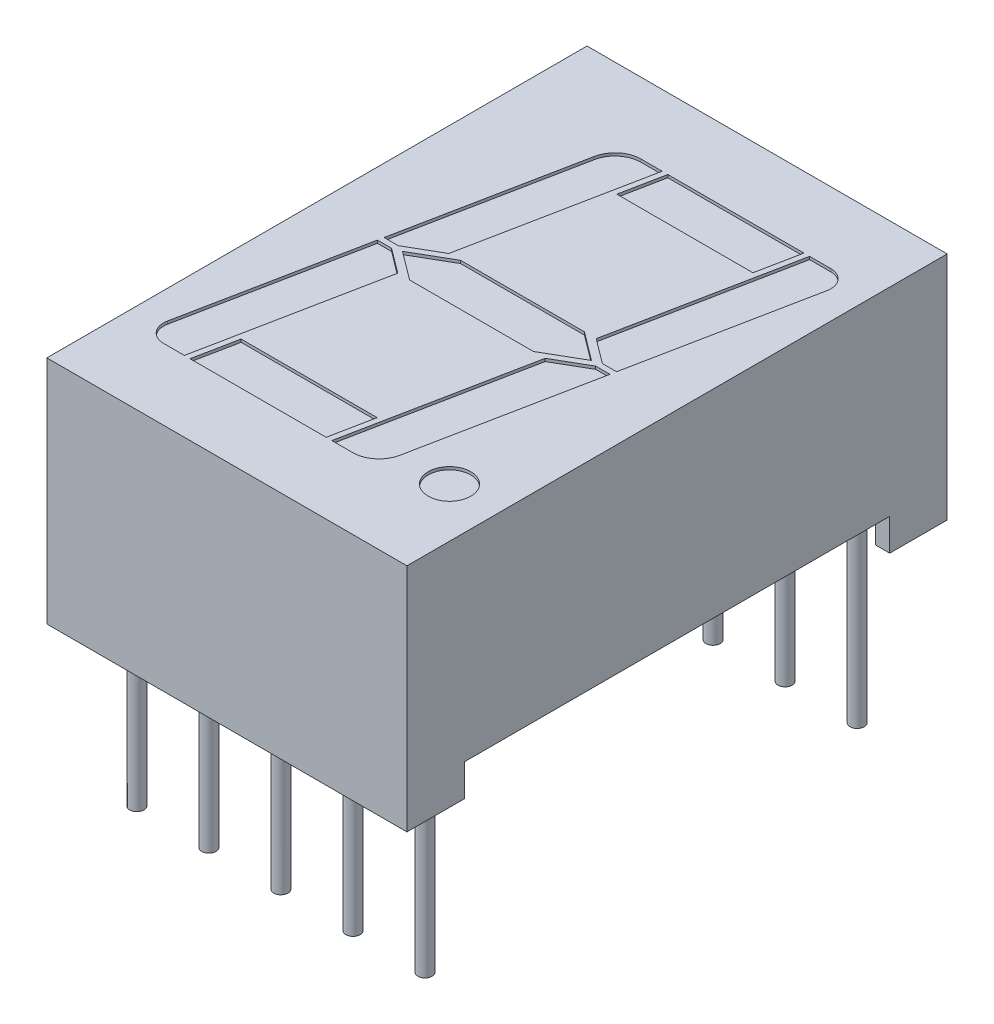
SolidWorks part; units mm, degrees
material "ABS"
ref_plane "Front Plane" through (0, 0, 0) normal (0, 0, 1) x (1, 0, 0)
ref_plane "Top Plane" through (0, 0, 0) normal (0, 1, 0) x (1, 0, 0)
ref_plane "Right Plane" through (0, 0, 0) normal (1, 0, 0) x (0, 0, -1)
sketch "Sketch1" plane through (0, 0, 0) normal (0, 1, 0) x (1, 0, 0)
  line L0 (0, 9.525) -> (0, -9.525) construction
  line L1 (-6.35, 9.525) -> (6.35, 9.525)
  line L2 (-6.35, 9.525) -> (-6.35, -9.525)
  line L3 (-6.35, -9.525) -> (6.35, -9.525)
  line L4 (6.35, 9.525) -> (6.35, -9.525)
  dimension "D1" = 12.7
  dimension "D2" = 19.05
extrude "Boss-Extrude1" add sketch "Sketch1" against normal blind 8.128
sketch "Sketch2" plane through (6.35, 0, 0) normal (1, 0, 0) x (0, 0, -1)
  line L0 (0, 0) -> (0, -7) construction
  line L1 (-9.525, -8.128) -> (9.525, -8.128) construction
  line L2 (-7.5, -7) -> (7.5, -7)
  line L3 (-7.5, -7) -> (-7.5, -8.128)
  line L4 (-7.5, -8.128) -> (7.5, -8.128)
  line L5 (7.5, -7) -> (7.5, -8.128)
  line L7 (0, -7) -> (0, -8.128) construction
  dimension "D1" = 15
  dimension "D2" = 7
extrude "Cut-Extrude1" cut sketch "Sketch2" against normal up to surface (12.7 mm away) up to face at (-6.35, -4.064, 0)
sketch "Sketch3" plane through (0, -7, 0) normal (0, -1, 0) x (1, 0, 0)
  line L0 (-6.35, 9.525) -> (6.35, 9.525) construction
  line L1 (-5.85, 9.025) -> (5.85, 9.025)
  line L2 (-5.85, 9.025) -> (-5.85, -9.025)
  line L3 (-5.85, -9.025) -> (5.85, -9.025)
  line L4 (5.85, 9.025) -> (5.85, -9.025)
  line L5 (-5.85, 9.025) -> (5.85, -9.025) construction
  line L6 (-5.85, -9.025) -> (5.85, 9.025) construction
  line L7 (-6.35, -9.525) -> (-6.35, 9.525) construction
  point P0 (0, 0)
  dimension "D1" = 0.5
  dimension "D2" = 0.5
extrude "Cut-Extrude2" cut sketch "Sketch3" against normal blind 0.5 and the other way up to surface (1.128 mm away) other way up to face at (0, -8.128, -8.5125)
fillet "Fillet1" radius 1 4 edges at (5.85, -6.5, 0) (0, -6.5, -9.025) (-5.85, -6.5, 0) (0, -6.5, 9.025)
fillet "Fillet2" radius 0.1 8 edges at (-5.85, -7.814, -9.025) (5.85, -7.814, -9.025) (5.85, -7.814, 9.025) (-5.85, -7.814, 9.025) (-5.5571, -6.7929, -8.7321) (5.5571, -6.7929, -8.7321) (5.5571, -6.7929, 8.7321) (-5.5571, -6.7929, 8.7321)
sketch "Sketch4" plane through (0, 0, 0) normal (0, 1, 0) x (1, 0, 0)
  line L0 (4.6, -6.275) -> (4.6, -7.025) construction
  line L1 (4.6, -6.275) -> (4.6, -5.525) construction
  line L2 (-6.35, -9.525) -> (6.35, -9.525) construction
  line L3 (4.6, -6.275) -> (5.35, -6.275) construction
  line L4 (4.6, -6.275) -> (3.85, -6.275) construction
  line L5 (-1.1006, -5.525) -> (-1.25, -6.275) construction
  line L6 (5.35, -6.275) -> (6.35, -6.275) construction
  line L7 (6.35, -9.525) -> (6.35, 9.525) construction
  line L8 (3.85, -6.275) -> (2.85, -6.275) construction
  line L9 (1.15, -6.275) -> (-3.65, -6.275) construction
  line L10 (2.85, -6.275) -> (1.35, -6.275) construction
  line L11 (1.35, -6.275) -> (1.15, -6.275) construction
  line L12 (-3.65, -6.275) -> (-3.85, -6.275) construction
  line L13 (-3.85, -6.275) -> (-5.35, -6.275) construction
  line L14 (-5.35, -6.275) -> (-6.35, -6.275) construction
  line L15 (-6.35, 9.525) -> (-6.35, -9.525) construction
  line L16 (1.25, 6.275) -> (1.1006, 5.525) construction
  line L17 (3.65, 6.275) -> (-1.15, 6.275) construction
  line L18 (3.65, 6.275) -> (3.85, 6.275) construction
  line L19 (3.85, 6.275) -> (5.35, 6.275) construction
  line L20 (-1.15, 6.275) -> (-1.35, 6.275) construction
  line L21 (-1.35, 6.275) -> (-2.85, 6.275) construction
  line L22 (3.7994, 7.025) -> (3.5006, 5.525)
  line L23 (-1.0006, 7.025) -> (-1.2994, 5.525)
  line L24 (-1.0006, 7.025) -> (3.7994, 7.025)
  line L25 (-1.2994, 5.525) -> (3.5006, 5.525)
  line L26 (1.2994, -5.525) -> (1.0006, -7.025)
  line L27 (-3.5006, -5.525) -> (-3.7994, -7.025)
  line L28 (-3.5006, -5.525) -> (1.2994, -5.525)
  line L29 (-3.7994, -7.025) -> (1.0006, -7.025)
  line L30 (2.6, 0) -> (-2.6, 0) construction
  line L31 (2.4506, -0.75) -> (1.2006, -7.025)
  line L32 (1.0006, -7.025) -> (1.2006, -7.025) construction
  line L33 (-3.7994, -7.025) -> (-3.9994, -7.025) construction
  line L34 (-2.7494, -0.75) -> (-3.9994, -7.025)
  line L35 (2.4506, -0.75) -> (2.7494, 0.75) construction
  line L36 (2.7494, 0.75) -> (3.9994, 7.025)
  line L37 (3.7994, 7.025) -> (3.9994, 7.025) construction
  line L38 (-2.7494, -0.75) -> (-2.4506, 0.75) construction
  line L39 (-2.4506, 0.75) -> (-1.2006, 7.025)
  line L40 (-1.0006, 7.025) -> (-1.2006, 7.025) construction
  line L41 (-2.6, 0) -> (-3.3335, 0) construction
  line L42 (-3.3335, 0) -> (-3.6, 0) construction
  line L43 (0, 0) -> (-0.1494, -0.75) construction
  line L44 (0.1494, 0.75) -> (1.1006, 5.525) construction
  line L45 (0, 0) -> (0.1494, 0.75) construction
  line L46 (-0.1494, -0.75) -> (-1.1006, -5.525) construction
  line L47 (2.6, 0) -> (3.3335, 0) construction
  line L48 (-3.6, 0) -> (-4.1, 0) construction
  line L49 (1.2006, -7.025) -> (1.9506, -7.025)
  line L50 (-3.9994, -7.025) -> (-4.7494, -7.025)
  line L51 (3.9994, 7.025) -> (4.7494, 7.025)
  line L52 (-1.2006, 7.025) -> (-1.9506, 7.025)
  line L53 (-2.0337, 0.75) -> (2.3325, 0.75)
  line L54 (-2.3325, -0.75) -> (2.0337, -0.75)
  line L55 (4.1195, 0.0981) -> (4.0805, -0.0981) construction
  line L56 (-4.0805, 0.0981) -> (-4.1195, -0.0981) construction
  line L57 (2.85, -6.275) -> (4.0805, -0.0981)
  line L58 (-5.35, -6.275) -> (-4.1195, -0.0981)
  line L59 (-4.0805, 0.0981) -> (-2.85, 6.275)
  line L60 (4.1195, 0.0981) -> (5.35, 6.275)
  line L61 (2.3325, 0.75) -> (2.7494, 0.75) construction
  line L62 (-2.0337, 0.75) -> (-2.4506, 0.75) construction
  line L63 (3.3335, 0) -> (3.6, 0) construction
  line L64 (3.6, 0) -> (4.1, 0) construction
  line L65 (2.3325, 0.75) -> (3.3335, 0)
  line L66 (3.3335, 0) -> (2.0337, -0.75)
  line L67 (3.6195, 0.0981) -> (3.5805, -0.0981) construction
  line L68 (2.7494, 0.75) -> (3.6195, 0.0981)
  line L69 (3.6195, 0.0981) -> (4.1195, 0.0981)
  line L70 (2.4506, -0.75) -> (3.5805, -0.0981)
  line L71 (3.5805, -0.0981) -> (4.0805, -0.0981)
  line L72 (-3.5805, 0.0981) -> (-3.6195, -0.0981) construction
  line L73 (-2.7494, -0.75) -> (-3.6195, -0.0981)
  line L74 (-3.6195, -0.0981) -> (-4.1195, -0.0981)
  line L75 (-4.0805, 0.0981) -> (-3.5805, 0.0981)
  line L76 (-3.5805, 0.0981) -> (-2.4506, 0.75)
  line L77 (-2.0337, 0.75) -> (-3.3335, 0)
  line L78 (-3.3335, 0) -> (-2.3325, -0.75)
  circle A0 centre (4.6, -6.275) radius 0.75
  arc A1 (4.7494, 7.025) -> (5.35, 6.275) centre (4.7494, 6.4095) cw
  arc A2 (-2.85, 6.275) -> (-1.9506, 7.025) centre (-1.9506, 6.1107) cw
  arc A3 (-5.35, -6.275) -> (-4.7494, -7.025) centre (-4.7345, -6.3976) ccw
  arc A4 (2.85, -6.275) -> (1.9506, -7.025) centre (1.9357, -6.0929) cw
  dimension "D1" = 1.5
  dimension "D11" = 0.25
  dimension "D2" = 2.5
  dimension "D3" = 1
  dimension "D4" = 1.5
  dimension "D5" = 4.8
  dimension "D6" = 8.2
  dimension "D7" = 0.2
  dimension "D8" = 0.2
  dimension "D9" = 1.5
  dimension "D10" = 0.75
  dimension "D12" = 0.5
extrude "Cut-Extrude3" cut sketch "Sketch4" against normal blind 0.1
sketch "Sketch5" plane through (0, -6.5, 0) normal (0, -1, 0) x (1, 0, 0)
  line L0 (0, 7.62) -> (0, -7.62) construction
  line L1 (0, -7.62) -> (2.54, -7.62) construction
  line L2 (2.54, -7.62) -> (5.08, -7.62) construction
  line L3 (0, -7.62) -> (-2.54, -7.62) construction
  line L4 (-2.54, -7.62) -> (-5.08, -7.62) construction
  line L5 (0, 7.62) -> (2.54, 7.62) construction
  line L6 (2.54, 7.62) -> (5.08, 7.62) construction
  line L7 (0, 7.62) -> (-2.54, 7.62) construction
  line L8 (-2.54, 7.62) -> (-5.08, 7.62) construction
  circle A0 centre (-5.08, 7.62) radius 0.25
  circle A1 centre (-2.54, 7.62) radius 0.25
  circle A2 centre (0, 7.62) radius 0.25
  circle A3 centre (2.54, 7.62) radius 0.25
  circle A4 centre (5.08, 7.62) radius 0.25
  circle A5 centre (-5.08, -7.62) radius 0.25
  circle A6 centre (-2.54, -7.62) radius 0.25
  circle A7 centre (0, -7.62) radius 0.25
  circle A8 centre (2.54, -7.62) radius 0.25
  circle A9 centre (5.08, -7.62) radius 0.25
  dimension "D3" = 0.5
  dimension "D1" = 15.24
  dimension "D2" = 10.16
extrude "Boss-Extrude2" add sketch "Sketch5" along normal offset from surface (7.5 mm away) 14 up to face at (2.7075, 0, 3.5717)
